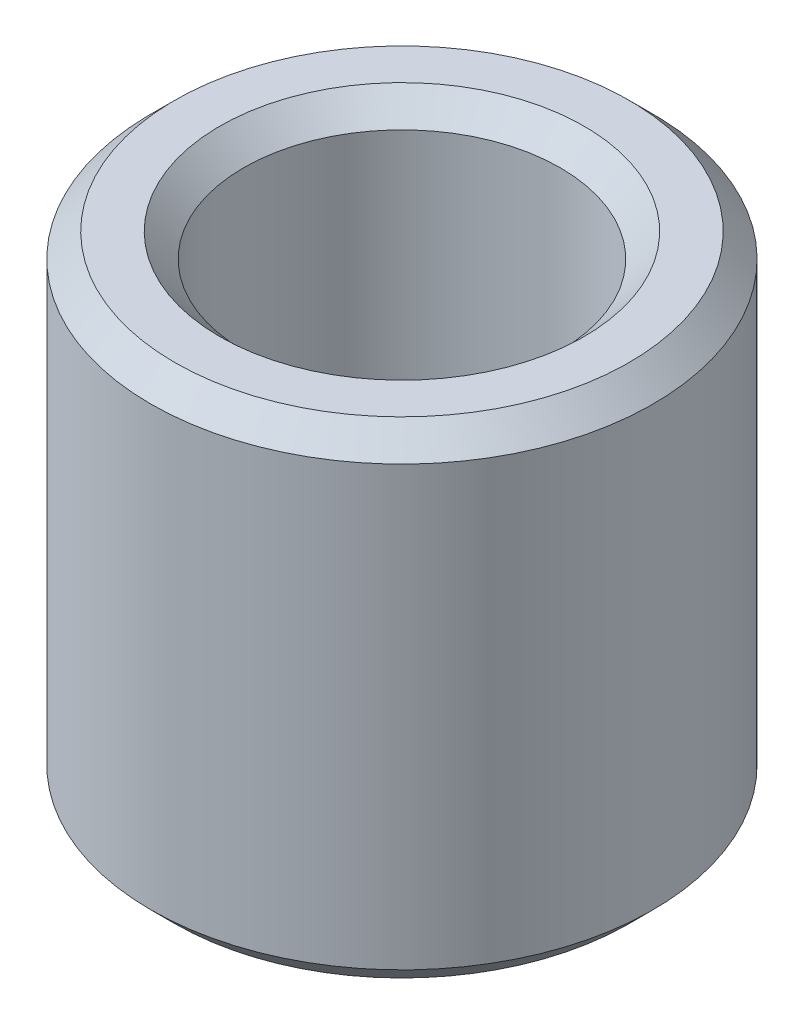
SolidWorks part; units mm, degrees
ref_plane "Front Plane" through (0, 0, 0) normal (0, 0, 1) x (1, 0, 0)
ref_plane "Top Plane" through (0, 0, 0) normal (0, 1, 0) x (1, 0, 0)
ref_plane "Right Plane" through (0, 0, 0) normal (1, 0, 0) x (0, 0, -1)
sketch "Sketch1" plane through (0, 0, 0) normal (0, 1, 0) x (1, 0, 0)
  circle A0 centre (0, 0) radius 7.5
  dimension "SLEEVE_OD" = 15
extrude "Boss-Extrude1" add sketch "Sketch1" along normal blind 14.5132
sketch "Sketch2" plane through (0, 0, 0) normal (0, 1, 0) x (1, 0, 0)
  circle A0 centre (0, 0) radius 4.727
  dimension "BORE_D" = 9.454
extrude "Cut-Extrude1" cut sketch "Sketch2" along normal through all
chamfer "Chamfer1" distance 0.7158 angle 45 4 edges at (0, 14.5132, 4.727) (0, 0, 4.727) (0, 0, 7.5) (0, 14.5132, 7.5)
